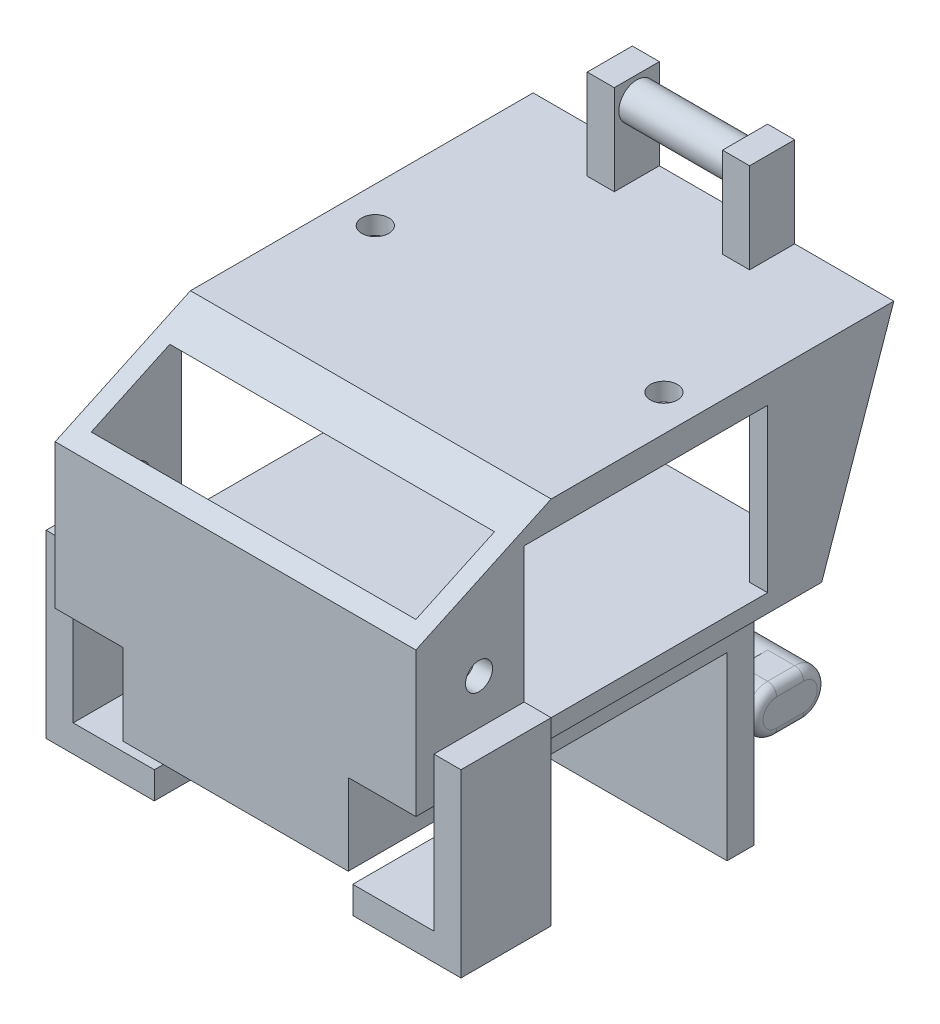
SolidWorks part; units mm, degrees
ref_plane "正面" through (0, 0, 0) normal (0, 0, 1) x (1, 0, 0)
ref_plane "平面" through (0, 0, 0) normal (0, 1, 0) x (1, 0, 0)
ref_plane "右側面" through (0, 0, 0) normal (1, 0, 0) x (0, 0, -1)
sketch "ｽｹｯﾁ1" plane through (0, 0, 0) normal (0, 1, 0) x (1, 0, 0)
  line L1 (0, 0) -> (25, 0)
  line L2 (0, 0) -> (0, 42)
  line L3 (0, 42) -> (25, 42)
  line L4 (25, 0) -> (25, 42)
  dimension "D1" = 25
  dimension "D2" = 42
extrude "ﾎﾞｽ - 押し出し1" add sketch "ｽｹｯﾁ1" along normal blind 9
sketch "ｽｹｯﾁ2" plane through (0, 0, -42) normal (0, 0, -1) x (-1, 0, 0)
  line L1 (-25, 9) -> (0, 9)
  line L2 (-25, 9) -> (-25, -20)
  line L3 (-25, -20) -> (0, -20)
  line L4 (0, 9) -> (0, -20)
  dimension "D1" = 29
extrude "ﾎﾞｽ - 押し出し2" add sketch "ｽｹｯﾁ2" along normal blind 3
sketch "ｽｹｯﾁ3" plane through (0, 9, 0) normal (0, 1, 0) x (1, 0, 0)
  line L1 (-7.5, 0) -> (32.5, 0)
  line L2 (-7.5, 0) -> (-7.5, 45)
  line L3 (-7.5, 45) -> (32.5, 45)
  line L4 (32.5, 0) -> (32.5, 45)
  line L5 (0, 0) -> (25, 0) construction
  line L6 (0, 45) -> (25, 45) construction
  line L7 (0, 45) -> (0, 0) construction
  dimension "D1" = 40
  dimension "D2" = 7.5
extrude "ﾎﾞｽ - 押し出し3" add sketch "ｽｹｯﾁ3" along normal blind 23
sketch "ｽｹｯﾁ4" plane through (0, 0, -45) normal (0, 0, -1) x (-1, 0, 0)
  line L0 (-32.5, 32) -> (7.5, 32) construction
  line L1 (5.5, 30) -> (-30.5, 30)
  line L2 (5.5, 30) -> (5.5, 11)
  line L3 (5.5, 11) -> (-30.5, 11)
  line L4 (-30.5, 30) -> (-30.5, 11)
  line L5 (7.5, 32) -> (7.5, 9) construction
  line L6 (-32.5, 32) -> (-32.5, 9) construction
  line L7 (0, 9) -> (7.5, 9) construction
  dimension "D1" = 2
  dimension "D2" = 2
  dimension "D3" = 2
  dimension "D4" = 2
extrude "ｶｯﾄ - 押し出し1" cut sketch "ｽｹｯﾁ4" against normal blind 43
sketch "ｽｹｯﾁ6" plane through (32.5, 0, 0) normal (1, 0, 0) x (0, 0, -1)
  line L0 (42, 0) -> (42, -20) construction
  line L1 (2, -6) -> (12, -6)
  line L2 (2, -6) -> (2, 14)
  line L3 (2, 14) -> (12, 14)
  line L4 (12, -6) -> (12, 14)
  line L5 (0, 9) -> (45, 9) construction
  dimension "D1" = 30
  dimension "D2" = 20
  dimension "D3" = 10
  dimension "D4" = 15
extrude "ﾎﾞｽ - 押し出し4" add sketch "ｽｹｯﾁ6" along normal blind 3
sketch "ｽｹｯﾁ7" plane through (0, -6, 0) normal (0, -1, 0) x (1, 0, 0)
  line L0 (35.5, -2) -> (32.5, -2) construction
  line L1 (32.5, -12) -> (23.5, -12)
  line L2 (32.5, -12) -> (32.5, -2)
  line L3 (32.5, -2) -> (23.5, -2)
  line L4 (23.5, -12) -> (23.5, -2)
  dimension "D1" = 9
extrude "ﾎﾞｽ - 押し出し5" add sketch "ｽｹｯﾁ7" against normal blind 3
ref_plane "平面1" through (12.5, 0, 0) normal (1, 0, 0) x (0, 0, -1)
mirror "ﾐﾗｰ1" about plane through (12.5, 0, 0) normal (1, 0, 0) of "ﾎﾞｽ - 押し出し4", "ﾎﾞｽ - 押し出し5"
sketch "ｽｹｯﾁ8" plane through (0, 32, 0) normal (0, 1, 0) x (1, 0, 0)
  line L0 (12.5, -15.95) -> (12.5, 15.95) construction
  line L1 (3.5, 53) -> (6.5, 53)
  line L2 (3.5, 53) -> (3.5, 48)
  line L3 (3.5, 48) -> (6.5, 48)
  line L4 (6.5, 53) -> (6.5, 48)
  line L5 (21.5, 48) -> (18.5, 48)
  line L6 (18.5, 53) -> (18.5, 48)
  line L7 (21.5, 53) -> (18.5, 53)
  line L8 (21.5, 53) -> (21.5, 48)
  line L10 (32.5, 45) -> (-7.5, 45) construction
  dimension "D1" = 5
  dimension "D2" = 3
  dimension "D3" = 12
  dimension "D4" = 8
extrude "ﾎﾞｽ - 押し出し6" add sketch "ｽｹｯﾁ8" along normal blind 10
sketch "ｽｹｯﾁ9" plane through (6.5, 0, 0) normal (1, 0, 0) x (0, 0, -1)
  line L0 (48, 42) -> (48, 32) construction
  line L1 (48, 42) -> (53, 42) construction
  circle A0 centre (50.5, 39.5) radius 2
  dimension "D1" = 4
  dimension "D2" = 2.5
  dimension "D3" = 2.5
extrude "ﾎﾞｽ - 押し出し7" add sketch "ｽｹｯﾁ9" along normal up to next (12 mm away)
sketch "ｽｹｯﾁ10" plane through (-7.5, 0, 0) normal (-1, 0, 0) x (0, 0, 1)
  line L0 (-2, 9) -> (0, 9) construction
  line L1 (0, 32) -> (0, 9) construction
  circle A0 centre (-7, 19) radius 1.5
  dimension "D1" = 3
  dimension "D2" = 10
  dimension "D3" = 7
extrude "ｶｯﾄ - 押し出し2" cut sketch "ｽｹｯﾁ10" against normal through all
sketch "ｽｹｯﾁ11" plane through (0, 0, -45) normal (0, 0, -1) x (-1, 0, 0)
  line L1 (-25, -20) -> (0, -20) construction
  line L2 (-12.5, 15.95) -> (-12.5, -15.95) construction
  circle A0 centre (-12.5, -10) radius 2.5
  dimension "D1" = 5
  dimension "D2" = 10
extrude "ﾎﾞｽ - 押し出し8" add sketch "ｽｹｯﾁ11" along normal blind 9
sketch "ｽｹｯﾁ12" plane through (12.5, 0, 0) normal (1, 0, 0) x (0, 0, -1)
  line L0 (45, -12.5) -> (45, -7.5) construction
  line L2 (45, -12.5) -> (54, -12.5) construction
  circle A0 centre (52, -10) radius 2.5
  dimension "D1" = 5
  dimension "D2" = 7
  dimension "D3" = 2.5
extrude "ﾎﾞｽ - 押し出し9" add sketch "ｽｹｯﾁ12" along normal blind 7
sketch "ｽｹｯﾁ13" plane through (19.5, 0, 0) normal (1, 0, 0) x (0, 0, -1)
  line L0 (52, -10) -> (49, -10) construction
  line L1 (52, -12.5) -> (49, -12.5)
  line L2 (52, -7.5) -> (49, -7.5)
  arc A0 (52, -12.5) -> (52, -7.5) centre (52, -10) ccw
  arc A1 (49, -7.5) -> (49, -12.5) centre (49, -10) ccw
  circle A2 centre (52, -10) radius 2.5 construction
  point P2 (50.5, -10)
  dimension "D1" = 2.5
  dimension "D2" = 3
extrude "ﾎﾞｽ - 押し出し10" add sketch "ｽｹｯﾁ13" along normal blind 4
fillet "ﾌｨﾚｯﾄ1" radius 1 4 edges at (23.5, -12.5, -50.5) (23.5, -10, -46.5) (23.5, -7.5, -50.5) (23.5, -10, -54.5)
mirror "ﾐﾗｰ2" about plane through (12.5, 0, 0) normal (1, 0, 0) of "ﾌｨﾚｯﾄ1", "ﾎﾞｽ - 押し出し10", "ﾎﾞｽ - 押し出し9"
sketch "ｽｹｯﾁ14" plane through (-7.5, 0, 0) normal (-1, 0, 0) x (0, 0, 1)
  line L0 (-15, 32) -> (0, 25)
  line L1 (-45, 32) -> (0, 32) construction
  line L2 (0, 32) -> (0, 9) construction
  line L3 (0, 25) -> (0, 32)
  line L4 (0, 32) -> (-15, 32)
  dimension "D1" = 15
  dimension "D2" = 7
extrude "ｶｯﾄ - 押し出し3" cut sketch "ｽｹｯﾁ14" against normal through all
sketch "ｽｹｯﾁ15" plane through (-7.5, 0, 0) normal (-1, 0, 0) x (0, 0, 1)
  line L0 (-45, 9) -> (-53, 32)
  line L1 (-53, 32) -> (-45, 32)
  line L2 (-45, 32) -> (-45, 9)
  dimension "D1" = 8
extrude "ﾎﾞｽ - 押し出し11" add sketch "ｽｹｯﾁ15" against normal blind 40
sketch "ｽｹｯﾁ17" plane through (0, 0, -45) normal (0, 0, 1) x (1, 0, 0)
  line L0 (30.5, 30) -> (30.5, 11) construction
  line L1 (-5.5, 11) -> (30.5, 11)
  line L2 (-5.5, 11) -> (-5.5, 30)
  line L3 (-5.5, 30) -> (30.5, 30)
  line L4 (30.5, 11) -> (30.5, 30)
extrude "ｶｯﾄ - 押し出し4" cut sketch "ｽｹｯﾁ17" against normal through all
sketch "ｽｹｯﾁ19" plane through (30.5, 0, 0) normal (-1, 0, 0) x (0, 0, 1)
  line L0 (-2, 11) -> (-45.6957, 11) construction
  line L1 (-39, 11) -> (-12, 11)
  line L2 (-39, 11) -> (-39, 29)
  line L3 (-39, 29) -> (-12, 29)
  line L4 (-12, 11) -> (-12, 29)
  line L5 (-2, 25.9333) -> (-2, 11) construction
  dimension "D1" = 27
  dimension "D2" = 10
  dimension "D3" = 18
extrude "ｶｯﾄ - 押し出し5" cut sketch "ｽｹｯﾁ19" against normal through all both and the other way through all
sketch "ｽｹｯﾁ20" plane through (0, 32, 0) normal (0, 1, 0) x (1, 0, 0)
  line L0 (-7.5, 53) -> (-7.5, 15) construction
  line L1 (32.5, 15) -> (32.5, 53) construction
  line L2 (3.5, 48) -> (6.5, 48) construction
  line L3 (18.5, 48) -> (21.5, 48) construction
  circle A0 centre (-3.5, 31.5) radius 1.5
  circle A1 centre (28.5, 31.5) radius 1.5
  dimension "D1" = 3
  dimension "D2" = 3
  dimension "D3" = 4
  dimension "D4" = 4
  dimension "D5" = 16.5
  dimension "D6" = 16.5
extrude "ｶｯﾄ - 押し出し6" cut sketch "ｽｹｯﾁ20" against normal blind 10 and the other way through all
